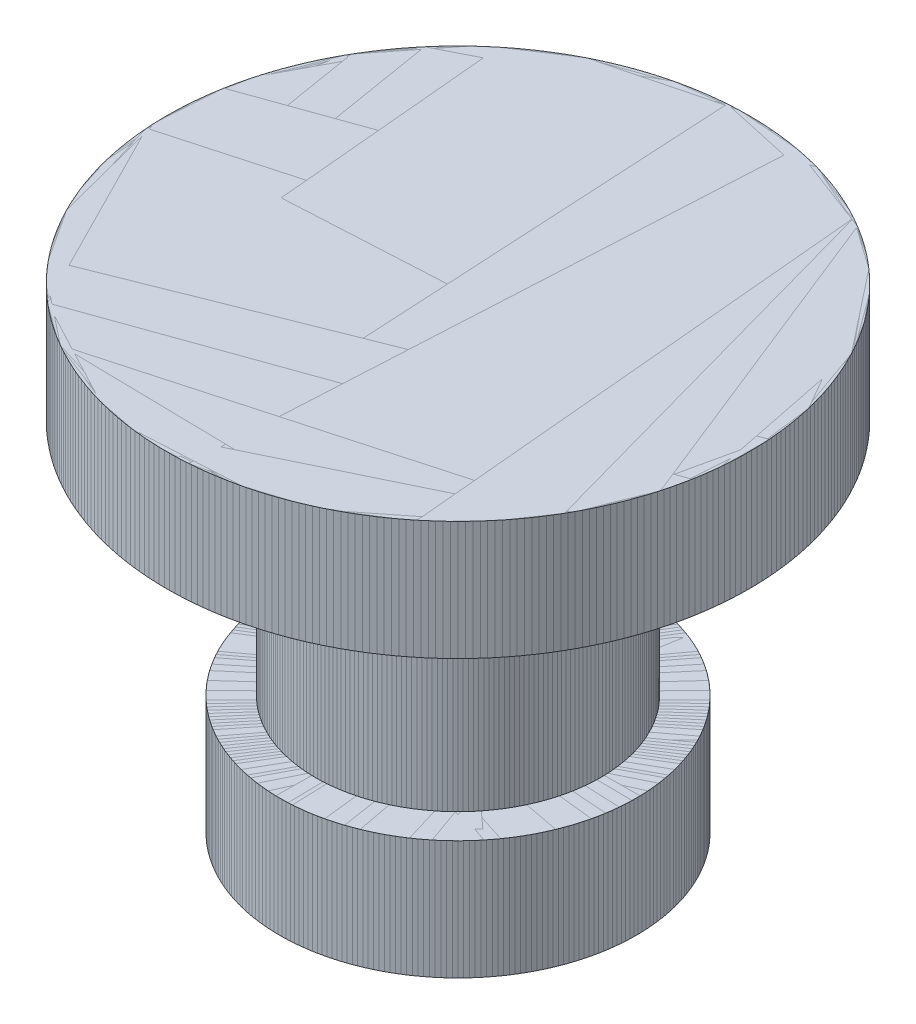
SolidWorks part; units mm, degrees
ref_plane "Front Plane" through (0, 0, 0) normal (0, 0, 1) x (1, 0, 0)
ref_plane "Top Plane" through (0, 0, 0) normal (0, 1, 0) x (1, 0, 0)
ref_plane "Right Plane" through (0, 0, 0) normal (1, 0, 0) x (0, 0, -1)
sketch "Sketch1" plane through (0, 0, 0) normal (0, 0, 1) x (1, 0, 0)
  line L0 (0, 0) -> (6.223, 0)
  line L1 (6.223, 0) -> (6.223, -2.54)
  line L2 (6.223, -2.54) -> (3.048, -2.54)
  line L3 (3.048, -2.54) -> (3.048, -7.62)
  line L4 (3.048, -7.62) -> (3.81, -7.62)
  line L5 (3.81, -7.62) -> (3.81, -10.16)
  line L6 (3.81, -10.16) -> (0, -10.16)
  line L7 (0, -10.16) -> (0, 0)
  dimension "D1" = 10.16
  dimension "D2" = 2.54
  dimension "D3" = 5.08
  dimension "D4" = 6.223
  dimension "D5" = 3.048
  dimension "D6" = 3.81
revolve "button body" add sketch "Sketch1" angle 360 about L7
ref_plane "spring path" through (4.318, 0, 0) normal (1, 0, 0) x (0, 0, -1)
sketch "Sketch2" plane through (4.318, 0, 0) normal (1, 0, 0) x (0, 0, -1)
  spline S0 degree 3 poles (2.9542, -4.563) (1.8538, -5.2739) (-1.4839, -5.7786) (3.0242, -6.9827) knots 0 0 0 0 1 1 1 1
ref_plane "spring cross section" through (0, 0, -3.0242) normal (0, 0, 1) x (1, 0, 0)
ref_axis "center axis" through (0, 0, 0) along (0, -1, 0)
pattern_circular "moar springs" count 4 over 360 about axis through (0, 0, 0) along (0, -1, 0) of bodies 101 102
ref_plane "curve hook" through (0, 0, 0) normal (0, 0, 1) x (1, 0, 0)
ref_point "curve start"
ref_plane "hook plane" through (0, 0, 0) normal (1, 0, 0) x (0, 0, -1)
sketch "Sketch12" plane through (0, 0, 0) normal (1, 0, 0) x (0, 0, -1)
  line L0 (0, -10.16) -> (0, -13.97)
  line L1 (-1.27, -15.24) -> (-5.08, -15.24)
  line L2 (-6.35, -13.97) -> (-6.35, -12.7)
  arc A0 (0, -13.97) -> (-1.27, -15.24) centre (-1.27, -13.97) cw
  arc A1 (-5.08, -15.24) -> (-6.35, -13.97) centre (-5.08, -13.97) cw
  point P8 (0, -15.24)
  point P11 (-6.35, -15.24)
  dimension "D2" = 1.27
  dimension "D4" = 1.27
  dimension "D1" = 5.08
  dimension "D3" = 2.54
  dimension "D5" = 3.81
sketch "Sketch13" plane through (0, -10.16, 0) normal (0, -1, 0) x (-1, 0, 0)
  circle A0 centre (0, 1.27) radius 1.27
